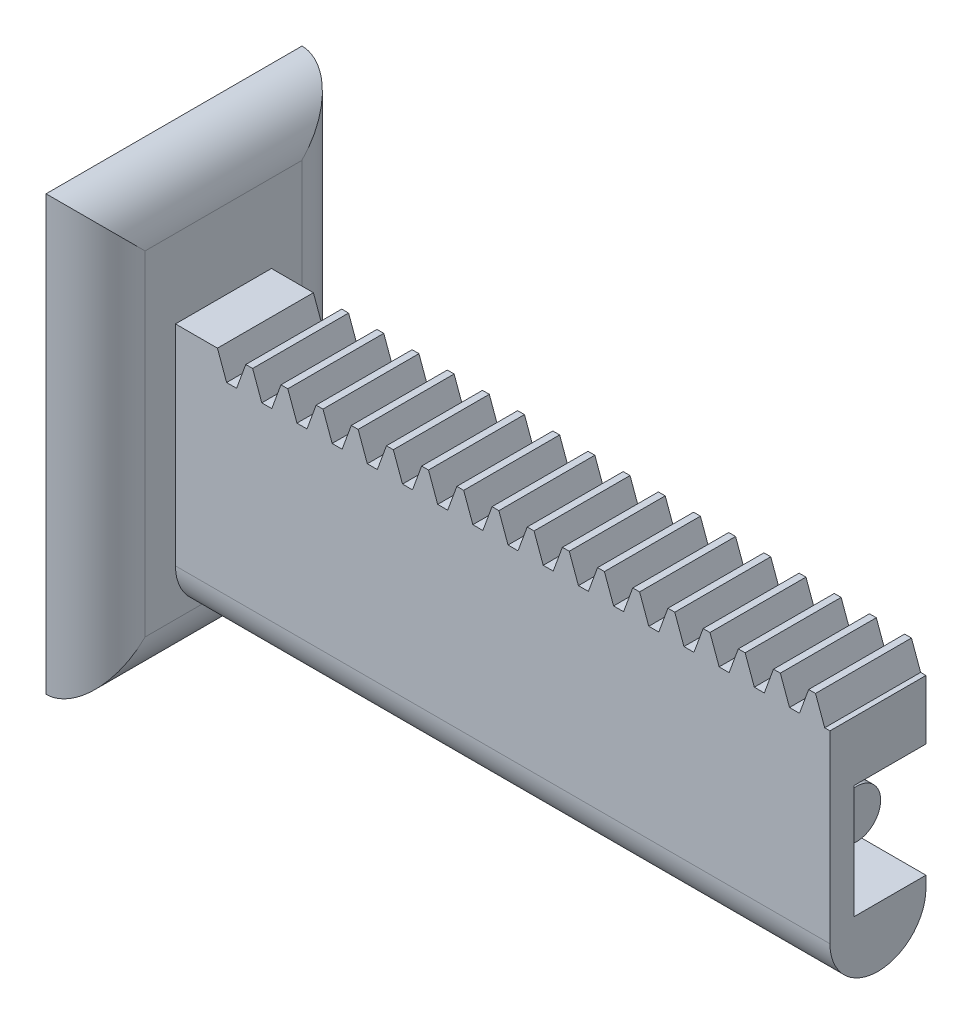
SolidWorks part; units mm, degrees
extrude "Blank" add sketch "BlankSke" against normal blind 4
sketch "BlankSke" plane through (0, 0, 0) normal (0, 0, 1) x (1, 0, 0)
  line L1 (0, 0) -> (44, 0)
  line L2 (0, 0) -> (0, 16.7)
  line L3 (0, 16.7) -> (44, 16.7)
  line L4 (44, 0) -> (44, 16.7)
  dimension "Length" = 44
  dimension "Blank_height" = 16.7
ref_plane "Plane1" through (0, 0, 0) normal (0, 0, 1) x (1, 0, 0)
ref_plane "Plane2" through (0, 0, 0) normal (0, 1, 0) x (1, 0, 0)
ref_plane "Plane3" through (0, 0, 0) normal (1, 0, 0) x (0, 0, -1)
sketch "HoldingSke" plane through (0, 0, 0) normal (0, 1, 0) x (1, 0, 0)
  line L0 (0, 0) -> (0.1988, 1.4147)
  line L1 (-15, 0) -> (100, 0) construction
  line L2 (0, 0) -> (-2.1039, 2.3779)
  line L3 (0, 0) -> (-11.863, 4.5341)
  line L4 (0, 0) -> (8.0072, 3.2351)
  line L5 (0, 0) -> (-23.7986, -8.8762)
  line L6 (0, 0) -> (-10.5278, -7.1032)
  line L9 (-71.009, 38.7566) -> (-29.6625, 53.8055)
  line L10 (-76.2, 3.0779) -> (-60.2, 3.0779)
  line L11 (0, 0) -> (-4, 0)
  line L12 (-76.2, 101.6) -> (-76.173, 101.6)
  line L13 (24.9733, 27.94) -> (52.9518, 28.4284)
  line L14 (24.9733, 27.94) -> (24.9743, 27.94)
  line L15 (24.9733, 27.94) -> (100.4006, 29.5858)
  circle A0 centre (0, 0) radius 19.05
  circle A1 centre (0, 0) radius 8
  circle A2 centre (0, 0) radius 12.7
  dimension "MPH" = 16
  dimension "Diameter" = 38.1
  dimension "Num_teeth" = 22
  dimension "Pitch" = 1.4286
  dimension "Show_teeth" = 998
  dimension "Thickness" = 12.7
  dimension "Ap" = 20
  dimension "Pitch_height" = 16
  dimension "Width" = 4
  dimension "Backlash" = 0.027
  dimension "Addendum_fac" = 1
  dimension "Dedendum_fac" = 1.25
  dimension "Clearance_fac" = 0.25
  dimension "Dedendum_add" = 0.001
  dimension "Length" = 44
  dimension "Module" = 0.7
sketch "TooCutSkeIll" plane through (0, 0, 0) normal (0, 0, 1) x (1, 0, 0)
  line L0 (-0.8789, 16.6816) -> (-0.3545, 15.2408)
  line L1 (-0.1891, 15.125) -> (0.1891, 15.125)
  line L2 (0.3545, 15.2408) -> (0.8789, 16.6816)
  line L3 (44, 16.7) -> (0, 16.7) construction
  line L4 (0, 0) -> (0, 64.897) construction
  line L5 (-13.208, 16) -> (12.954, 16) construction
  line L6 (0, 0) -> (44, 0) construction
  line L7 (0.6308, 16) -> (0.6308, 48.7463) construction
  line L8 (-0.6308, 16) -> (-0.6308, 48.7463) construction
  line L9 (0.9052, 16.7) -> (0.9052, 16.7254)
  line L10 (-0.9052, 16.7) -> (-0.9052, 16.7254)
  line L11 (-0.9052, 16.7254) -> (0.9052, 16.7254)
  arc A0 (0.1891, 15.125) -> (0.3545, 15.2408) centre (0.1891, 15.301) ccw
  arc A1 (-0.3545, 15.2408) -> (-0.1891, 15.125) centre (-0.1891, 15.301) ccw
  arc A2 (0.9052, 16.7) -> (0.8789, 16.6816) centre (0.9052, 16.672) ccw
  arc A3 (-0.8789, 16.6816) -> (-0.9052, 16.7) centre (-0.9052, 16.672) ccw
  dimension "Pitch_height" = 16
  dimension "Addendum_plus" = 0.7254
  dimension "Pressure_angle" = 20
  dimension "Gap_width" = 1.2616
  dimension "Dedendum" = 0.875
extrude "ToothCutIll" [suppressed] cut sketch "TooCutSkeIll" against normal through all
sketch "TooCutSkeSim" plane through (0, 0, 0) normal (0, 0, 1) x (1, 0, 0)
  line L0 (0.3123, 15.125) -> (-0.3123, 15.125)
  line L1 (0.8948, 16.7254) -> (0.3123, 15.125)
  line L2 (0, 17.4625) -> (0, 53.467) construction
  line L3 (0.8948, 16.7254) -> (-0.8948, 16.7254)
  line L6 (-0.8948, 16.7254) -> (-0.3123, 15.125)
  line L9 (-0.6308, 16) -> (0.6308, 16) construction
  line L10 (0, 0) -> (44, 0) construction
  line L11 (0.6308, 16) -> (0.6308, 53.467) construction
  line L12 (-0.6308, 16) -> (-0.6308, 53.467) construction
  dimension "Pitch_height" = 16
  dimension "Addendum_plus" = 0.7254
  dimension "Pressure_angle" = 20
  dimension "Gap_width" = 1.2616
  dimension "Dedendum" = 0.875
extrude "ToothCutSim" cut sketch "TooCutSkeSim" against normal through all
pattern_linear "TeethCuts" count 22 spacing 2.1991 along (1, 0, 0) of "ToothCutIll", "ToothCutSim"
sketch "Croquis1" plane through (0, 0, 0) normal (0, -1, 0) x (1, 0, 0)
  line L4 (44, 0) -> (0, 0)
  line L5 (0, 0) -> (0, -4)
  line L6 (0, -4) -> (44, -4)
  line L7 (44, -4) -> (44, 0)
  line L8 (44, 0) -> (0, 0)
  line L9 (0, 0) -> (0, -4)
  line L10 (0, -4) -> (44, -4)
  line L11 (44, -4) -> (44, 0)
  dimension "D1" = 0
sketch "Croquis2" plane through (0, 0, 0) normal (0, -1, 0) x (1, 0, 0)
  line L4 (44, 0) -> (0, 0)
  line L5 (0, 0) -> (0, -4)
  line L6 (0, -4) -> (44, -4)
  line L7 (44, -4) -> (44, 0)
  line L8 (44, 0) -> (0, 0)
  line L9 (0, 0) -> (0, -4)
  line L10 (0, -4) -> (44, -4)
  line L11 (44, -4) -> (44, 0)
  dimension "D1" = 0
extrude "Cortar-Extruir2" cut sketch "Croquis2" against normal blind 0.6
sketch "Croquis3" plane through (44, 0, 0) normal (1, 0, 0) x (0, 0, -1)
  line L0 (0, 7.8625) -> (4, 7.8625)
  line L1 (0, 0.6) -> (0, 15.125) construction
  line L2 (4, 0.6) -> (4, 15.125) construction
  line L3 (1.5, 4.3125) -> (1.5, 11.4125)
  line L5 (1.5, 11.4125) -> (4, 11.4125)
  line L6 (1.5, 11.4125) -> (1.5, 4.3125)
  line L7 (1.5, 4.3125) -> (4, 4.3125)
  line L8 (4, 11.4125) -> (4, 4.3125)
  point P9 (0, 7.8625)
  line M3 (0, 15.125) -> (0, 0.6)
  dimension "D1" = 2.5
  dimension "D2" = 7.1
extrude "Cortar-Extruir3" cut sketch "Croquis3" against normal blind 37 contours L8 L5 L0 M3 | L8 L0 L7 M3 region at (44, 9.6375, -2.75) region at (44, 6.0875, -2.75)
ref_plane "Plano1" through (0, 0, 0) normal (0, 0, 1) x (1, 0, 0)
sketch "Croquis4" plane through (0, 0, 0) normal (0, 0, 1) x (1, 0, 0)
  line L0 (0, 15.125) -> (0, 0.6) construction
  line L1 (5.7118, 15.125) -> (0, 15.125)
  line L2 (5.7118, 15.125) -> (5.7118, 16.7)
  line L3 (5.7118, 16.7) -> (0, 16.7)
  line L4 (0, 15.125) -> (0, 16.7)
extrude "Saliente-Extruir4" add sketch "Croquis4" against normal up to vertex (4 mm away) up to point (5.7118, 16.7, -4)
sketch "Croquis5" plane through (0, 0, -1.5) normal (0, 0, -1) x (-1, 0, 0)
  line L0 (-44, 7.8625) -> (-39.57, 7.8625) construction
  line L1 (-44, 4.3125) -> (-44, 11.4125) construction
  line L2 (-39.57, 5.7125) -> (-39.57, 10.0125) construction
  line L4 (-39.57, 10.0125) -> (-38.45, 10.0125)
  line L5 (-39.57, 5.7125) -> (-38.45, 5.7125)
  line L6 (-38.45, 10.0125) -> (-38.45, 5.7125)
  line L7 (-39.57, 10.0125) -> (-39.57, 5.7125)
  point P7 (-39.57, 7.8625)
  point P9 (-39.57, 7.8625)
  dimension "D1" = 4.43
  dimension "D2" = 4.3
  dimension "D3" = 1.12
  dimension "D4" = 1.12
extrude "Saliente-Extruir5" add sketch "Croquis5" along normal blind 4.2
sketch "Croquis14" plane through (39.57, 0, 0) normal (1, 0, 0) x (0, 0, -1)
  line L0 (5.7, 7.8625) -> (1.5, 7.8625) construction
  line L1 (5.7, 10.0125) -> (5.7, 5.7125) construction
  line L2 (1.5, 10.0125) -> (1.5, 5.7125) construction
  circle A0 centre (3.6, 7.8625) radius 1.5
  dimension "D1" = 3
extrude "Saliente-Extruir11" add sketch "Croquis14" along normal blind 2.5
sketch "Croquis13" plane through (39.57, 0, 0) normal (1, 0, 0) x (0, 0, -1)
  line L0 (5.7, 7.8625) -> (1.5, 7.8625) construction
  line L1 (5.7, 10.0125) -> (5.7, 5.7125) construction
  line L2 (1.5, 10.0125) -> (1.5, 5.7125) construction
  circle A0 centre (3.6, 7.8625) radius 0.75
  dimension "D1" = 1.5
sketch "Croquis15" plane through (0, 0, 0) normal (0, 0, 1) x (1, 0, 0)
  line L0 (44, 0.6) -> (0, 0.6) construction
  line L1 (0, 16.7) -> (3.0889, 16.7)
  line L2 (0, 16.7) -> (0, 0.6)
  line L3 (0, 0.6) -> (3.0889, 0.6)
  line L4 (3.0889, 16.7) -> (3.0889, 0.6)
extrude "Saliente-Extruir12" add sketch "Croquis15" along normal blind 5
sketch "Croquis16" plane through (0, 0, -4) normal (0, 0, -1) x (-1, 0, 0)
  line L0 (-5.7118, 16.7) -> (0, 16.7) construction
  line L1 (0, 0.6) -> (-2.8559, 0.6)
  line L2 (0, 0.6) -> (0, 16.7)
  line L3 (0, 16.7) -> (-2.8559, 16.7)
  line L4 (-2.8559, 0.6) -> (-2.8559, 16.7)
extrude "Saliente-Extruir13" add sketch "Croquis16" along normal blind 5
sketch "Croquis17" plane through (0, 0, -4) normal (0, 0, -1) x (-1, 0, 0)
  line L78 (-44, 0.6) -> (-2.8559, 0.6)
  line L79 (-2.8559, 0.6) -> (-2.8559, 16.7)
  line L80 (-2.8559, 16.7) -> (-5.7118, 16.7)
  line L81 (-5.7118, 16.7) -> (-6.285, 15.125)
  line L82 (-6.285, 15.125) -> (-6.9096, 15.125)
  line L83 (-6.9096, 15.125) -> (-7.4829, 16.7)
  line L84 (-7.4829, 16.7) -> (-7.9109, 16.7)
  line L85 (-7.9109, 16.7) -> (-8.4842, 15.125)
  line L86 (-8.4842, 15.125) -> (-9.1088, 15.125)
  line L87 (-9.1088, 15.125) -> (-9.682, 16.7)
  line L88 (-9.682, 16.7) -> (-10.11, 16.7)
  line L89 (-10.11, 16.7) -> (-10.6833, 15.125)
  line L90 (-10.6833, 15.125) -> (-11.3079, 15.125)
  line L91 (-11.3079, 15.125) -> (-11.8811, 16.7)
  line L92 (-11.8811, 16.7) -> (-12.3091, 16.7)
  line L93 (-12.3091, 16.7) -> (-12.8824, 15.125)
  line L94 (-12.8824, 15.125) -> (-13.507, 15.125)
  line L95 (-13.507, 15.125) -> (-14.0802, 16.7)
  line L96 (-14.0802, 16.7) -> (-14.5082, 16.7)
  line L97 (-14.5082, 16.7) -> (-15.0815, 15.125)
  line L98 (-15.0815, 15.125) -> (-15.7061, 15.125)
  line L99 (-15.7061, 15.125) -> (-16.2794, 16.7)
  line L100 (-16.2794, 16.7) -> (-16.7074, 16.7)
  line L101 (-16.7074, 16.7) -> (-17.2806, 15.125)
  line L102 (-17.2806, 15.125) -> (-17.9052, 15.125)
  line L103 (-17.9052, 15.125) -> (-18.4785, 16.7)
  line L104 (-18.4785, 16.7) -> (-18.9065, 16.7)
  line L105 (-18.9065, 16.7) -> (-19.4797, 15.125)
  line L106 (-19.4797, 15.125) -> (-20.1043, 15.125)
  line L107 (-20.1043, 15.125) -> (-20.6776, 16.7)
  line L108 (-20.6776, 16.7) -> (-21.1056, 16.7)
  line L109 (-21.1056, 16.7) -> (-21.6788, 15.125)
  line L110 (-21.6788, 15.125) -> (-22.3035, 15.125)
  line L111 (-22.3035, 15.125) -> (-22.8767, 16.7)
  line L112 (-22.8767, 16.7) -> (-23.3047, 16.7)
  line L113 (-23.3047, 16.7) -> (-23.878, 15.125)
  line L114 (-23.878, 15.125) -> (-24.5026, 15.125)
  line L115 (-24.5026, 15.125) -> (-25.0758, 16.7)
  line L116 (-25.0758, 16.7) -> (-25.5038, 16.7)
  line L117 (-25.5038, 16.7) -> (-26.0771, 15.125)
  line L118 (-26.0771, 15.125) -> (-26.7017, 15.125)
  line L119 (-26.7017, 15.125) -> (-27.2749, 16.7)
  line L120 (-27.2749, 16.7) -> (-27.7029, 16.7)
  line L121 (-27.7029, 16.7) -> (-28.2762, 15.125)
  line L122 (-28.2762, 15.125) -> (-28.9008, 15.125)
  line L123 (-28.9008, 15.125) -> (-29.4741, 16.7)
  line L124 (-29.4741, 16.7) -> (-29.9021, 16.7)
  line L125 (-29.9021, 16.7) -> (-30.4753, 15.125)
  line L126 (-30.4753, 15.125) -> (-31.0999, 15.125)
  line L127 (-31.0999, 15.125) -> (-31.6732, 16.7)
  line L128 (-31.6732, 16.7) -> (-32.1012, 16.7)
  line L129 (-32.1012, 16.7) -> (-32.6744, 15.125)
  line L130 (-32.6744, 15.125) -> (-33.299, 15.125)
  line L131 (-33.299, 15.125) -> (-33.8723, 16.7)
  line L132 (-33.8723, 16.7) -> (-34.3003, 16.7)
  line L133 (-34.3003, 16.7) -> (-34.8735, 15.125)
  line L134 (-34.8735, 15.125) -> (-35.4981, 15.125)
  line L135 (-35.4981, 15.125) -> (-36.0714, 16.7)
  line L136 (-36.0714, 16.7) -> (-36.4994, 16.7)
  line L137 (-36.4994, 16.7) -> (-37.0726, 15.125)
  line L138 (-37.0726, 15.125) -> (-37.6973, 15.125)
  line L139 (-37.6973, 15.125) -> (-38.2705, 16.7)
  line L140 (-38.2705, 16.7) -> (-38.6985, 16.7)
  line L141 (-38.6985, 16.7) -> (-39.2718, 15.125)
  line L142 (-39.2718, 15.125) -> (-39.8964, 15.125)
  line L143 (-39.8964, 15.125) -> (-40.4696, 16.7)
  line L144 (-40.4696, 16.7) -> (-40.8976, 16.7)
  line L145 (-40.8976, 16.7) -> (-41.4709, 15.125)
  line L146 (-41.4709, 15.125) -> (-42.0955, 15.125)
  line L147 (-42.0955, 15.125) -> (-42.6687, 16.7)
  line L148 (-42.6687, 16.7) -> (-43.0967, 16.7)
  line L149 (-43.0967, 16.7) -> (-43.67, 15.125)
  line L150 (-43.67, 15.125) -> (-44, 15.125)
  line L151 (-44, 15.125) -> (-44, 11.4125)
  line L152 (-44, 11.4125) -> (-7, 11.4125)
  line L153 (-7, 11.4125) -> (-7, 4.3125)
  line L154 (-7, 4.3125) -> (-44, 4.3125)
  line L155 (-44, 4.3125) -> (-44, 0.6)
  line L156 (-44, 0.6) -> (-2.8559, 0.6)
  line L157 (-2.8559, 0.6) -> (-2.8559, 16.7)
  line L158 (-2.8559, 16.7) -> (-5.7118, 16.7)
  line L159 (-5.7118, 16.7) -> (-6.285, 15.125)
  line L160 (-6.285, 15.125) -> (-6.9096, 15.125)
  line L161 (-6.9096, 15.125) -> (-7.4829, 16.7)
  line L162 (-7.4829, 16.7) -> (-7.9109, 16.7)
  line L163 (-7.9109, 16.7) -> (-8.4842, 15.125)
  line L164 (-8.4842, 15.125) -> (-9.1088, 15.125)
  line L165 (-9.1088, 15.125) -> (-9.682, 16.7)
  line L166 (-9.682, 16.7) -> (-10.11, 16.7)
  line L167 (-10.11, 16.7) -> (-10.6833, 15.125)
  line L168 (-10.6833, 15.125) -> (-11.3079, 15.125)
  line L169 (-11.3079, 15.125) -> (-11.8811, 16.7)
  line L170 (-11.8811, 16.7) -> (-12.3091, 16.7)
  line L171 (-12.3091, 16.7) -> (-12.8824, 15.125)
  line L172 (-12.8824, 15.125) -> (-13.507, 15.125)
  line L173 (-13.507, 15.125) -> (-14.0802, 16.7)
  line L174 (-14.0802, 16.7) -> (-14.5082, 16.7)
  line L175 (-14.5082, 16.7) -> (-15.0815, 15.125)
  line L176 (-15.0815, 15.125) -> (-15.7061, 15.125)
  line L177 (-15.7061, 15.125) -> (-16.2794, 16.7)
  line L178 (-16.2794, 16.7) -> (-16.7074, 16.7)
  line L179 (-16.7074, 16.7) -> (-17.2806, 15.125)
  line L180 (-17.2806, 15.125) -> (-17.9052, 15.125)
  line L181 (-17.9052, 15.125) -> (-18.4785, 16.7)
  line L182 (-18.4785, 16.7) -> (-18.9065, 16.7)
  line L183 (-18.9065, 16.7) -> (-19.4797, 15.125)
  line L184 (-19.4797, 15.125) -> (-20.1043, 15.125)
  line L185 (-20.1043, 15.125) -> (-20.6776, 16.7)
  line L186 (-20.6776, 16.7) -> (-21.1056, 16.7)
  line L187 (-21.1056, 16.7) -> (-21.6788, 15.125)
  line L188 (-21.6788, 15.125) -> (-22.3035, 15.125)
  line L189 (-22.3035, 15.125) -> (-22.8767, 16.7)
  line L190 (-22.8767, 16.7) -> (-23.3047, 16.7)
  line L191 (-23.3047, 16.7) -> (-23.878, 15.125)
  line L192 (-23.878, 15.125) -> (-24.5026, 15.125)
  line L193 (-24.5026, 15.125) -> (-25.0758, 16.7)
  line L194 (-25.0758, 16.7) -> (-25.5038, 16.7)
  line L195 (-25.5038, 16.7) -> (-26.0771, 15.125)
  line L196 (-26.0771, 15.125) -> (-26.7017, 15.125)
  line L197 (-26.7017, 15.125) -> (-27.2749, 16.7)
  line L198 (-27.2749, 16.7) -> (-27.7029, 16.7)
  line L199 (-27.7029, 16.7) -> (-28.2762, 15.125)
  line L200 (-28.2762, 15.125) -> (-28.9008, 15.125)
  line L201 (-28.9008, 15.125) -> (-29.4741, 16.7)
  line L202 (-29.4741, 16.7) -> (-29.9021, 16.7)
  line L203 (-29.9021, 16.7) -> (-30.4753, 15.125)
  line L204 (-30.4753, 15.125) -> (-31.0999, 15.125)
  line L205 (-31.0999, 15.125) -> (-31.6732, 16.7)
  line L206 (-31.6732, 16.7) -> (-32.1012, 16.7)
  line L207 (-32.1012, 16.7) -> (-32.6744, 15.125)
  line L208 (-32.6744, 15.125) -> (-33.299, 15.125)
  line L209 (-33.299, 15.125) -> (-33.8723, 16.7)
  line L210 (-33.8723, 16.7) -> (-34.3003, 16.7)
  line L211 (-34.3003, 16.7) -> (-34.8735, 15.125)
  line L212 (-34.8735, 15.125) -> (-35.4981, 15.125)
  line L213 (-35.4981, 15.125) -> (-36.0714, 16.7)
  line L214 (-36.0714, 16.7) -> (-36.4994, 16.7)
  line L215 (-36.4994, 16.7) -> (-37.0726, 15.125)
  line L216 (-37.0726, 15.125) -> (-37.6973, 15.125)
  line L217 (-37.6973, 15.125) -> (-38.2705, 16.7)
  line L218 (-38.2705, 16.7) -> (-38.6985, 16.7)
  line L219 (-38.6985, 16.7) -> (-39.2718, 15.125)
  line L220 (-39.2718, 15.125) -> (-39.8964, 15.125)
  line L221 (-39.8964, 15.125) -> (-40.4696, 16.7)
  line L222 (-40.4696, 16.7) -> (-40.8976, 16.7)
  line L223 (-40.8976, 16.7) -> (-41.4709, 15.125)
  line L224 (-41.4709, 15.125) -> (-42.0955, 15.125)
  line L225 (-42.0955, 15.125) -> (-42.6687, 16.7)
  line L226 (-42.6687, 16.7) -> (-43.0967, 16.7)
  line L227 (-43.0967, 16.7) -> (-43.67, 15.125)
  line L228 (-43.67, 15.125) -> (-44, 15.125)
  line L229 (-44, 15.125) -> (-44, 11.4125)
  line L230 (-44, 11.4125) -> (-7, 11.4125)
  line L231 (-7, 11.4125) -> (-7, 4.3125)
  line L232 (-7, 4.3125) -> (-44, 4.3125)
  line L233 (-44, 4.3125) -> (-44, 0.6)
  dimension "D1" = 0
extrude "Saliente-Extruir14" add sketch "Croquis17" along normal blind 2
sketch "Croquis18" plane through (38.45, 0, 0) normal (-1, 0, 0) x (0, 0, 1)
  line L4 (-1.5, 5.7125) -> (-1.5, 10.0125)
  line L5 (-1.5, 10.0125) -> (-5.7, 10.0125)
  line L6 (-5.7, 10.0125) -> (-5.7, 5.7125)
  line L7 (-5.7, 5.7125) -> (-1.5, 5.7125)
  line L8 (-1.5, 5.7125) -> (-1.5, 10.0125)
  line L9 (-1.5, 10.0125) -> (-5.7, 10.0125)
  line L10 (-5.7, 10.0125) -> (-5.7, 5.7125)
  line L11 (-5.7, 5.7125) -> (-1.5, 5.7125)
  dimension "D1" = 0
extrude "Saliente-Extruir15" add sketch "Croquis18" along normal blind 2
sketch "Croquis19" plane through (0, 16.7, 0) normal (0, 1, 0) x (1, 0, 0)
  line L0 (2.8559, 9) -> (2.8559, 6) construction
  line L1 (0, 9) -> (2.8559, 9)
  line L2 (0, 9) -> (0, -5)
  line L3 (0, -5) -> (2.8559, -5)
  line L4 (2.8559, 9) -> (2.8559, -5)
  line L5 (0, 9) -> (2.8559, 9) construction
extrude "Saliente-Extruir16" add sketch "Croquis19" along normal blind 8
sketch "Croquis20" plane through (0, 0, -9) normal (0, 0, -1) x (-1, 0, 0)
  line L4 (0, 0.6) -> (0, 24.7)
  line L5 (0, 24.7) -> (-2.8559, 24.7)
  line L6 (-2.8559, 24.7) -> (-2.8559, 0.6)
  line L7 (-2.8559, 0.6) -> (0, 0.6)
  line L8 (0, 0.6) -> (0, 24.7)
  line L9 (0, 24.7) -> (-2.8559, 24.7)
  line L10 (-2.8559, 24.7) -> (-2.8559, 0.6)
  line L11 (-2.8559, 0.6) -> (0, 0.6)
  dimension "D1" = 0
extrude "Saliente-Extruir18" add sketch "Croquis20" along normal blind 2
sketch "Croquis21" plane through (0, 0.6, 0) normal (0, -1, 0) x (1, 0, 0)
  line L0 (3.0889, 0) -> (2.8559, -6)
  line L1 (0, 5) -> (0, -11) construction
  line L2 (2.8559, -11) -> (2.8559, -6) construction
  line L3 (2.8559, -11) -> (0, -11) construction
  line L4 (0, 5) -> (3.0889, 5) construction
  line L5 (3.0889, 5) -> (3.0889, 0) construction
  line L6 (0, 5) -> (0, -11)
  line L7 (2.8559, -11) -> (2.8559, -6)
  line L8 (2.8559, -11) -> (0, -11)
  line L9 (0, 5) -> (3.0889, 5)
  line L10 (3.0889, 5) -> (3.0889, 0)
extrude "Saliente-Extruir19" add sketch "Croquis21" along normal blind 3
ref_plane "Plano2" through (0, 0, 0) normal (-1, 0, 0) x (0, 0, 1)
sketch "Croquis22" plane through (0, 0, 0) normal (-1, 0, 0) x (0, 0, 1)
  line L4 (5, -2.4) -> (5, 24.7)
  line L5 (5, 24.7) -> (-11, 24.7)
  line L6 (-11, 24.7) -> (-11, -2.4)
  line L7 (-11, -2.4) -> (5, -2.4)
  line L8 (5, -2.4) -> (5, 24.7)
  line L9 (5, 24.7) -> (-11, 24.7)
  line L10 (-11, 24.7) -> (-11, -2.4)
  line L11 (-11, -2.4) -> (5, -2.4)
  dimension "D1" = 0
sketch "Croquis26" plane through (0, 0, 0) normal (-1, 0, 0) x (0, 0, 1)
  line L4 (5, -2.4) -> (5, 24.7)
  line L5 (5, 24.7) -> (-11, 24.7)
  line L6 (-11, 24.7) -> (-11, -2.4)
  line L7 (-11, -2.4) -> (5, -2.4)
  line L8 (5, -2.4) -> (5, 24.7)
  line L9 (5, 24.7) -> (-11, 24.7)
  line L10 (-11, 24.7) -> (-11, -2.4)
  line L11 (-11, -2.4) -> (5, -2.4)
  dimension "D1" = 0
ref_plane "Plano3" through (2.8559, 0.6, -6) normal (0.0388, 0, 0.9992) x (0.9992, 0, -0.0388)
ref_plane "Plano4" through (0, 0, 0) normal (-1, 0, 0) x (0, 0, 1)
sketch "Croquis29" plane through (0, 0, 0) normal (-1, 0, 0) x (0, 0, 1)
  line L4 (5, -2.4) -> (5, 24.7)
  line L5 (5, 24.7) -> (-11, 24.7)
  line L6 (-11, 24.7) -> (-11, -2.4)
  line L7 (-11, -2.4) -> (5, -2.4)
  line L8 (5, -2.4) -> (5, 24.7)
  line L9 (5, 24.7) -> (-11, 24.7)
  line L10 (-11, 24.7) -> (-11, -2.4)
  line L11 (-11, -2.4) -> (5, -2.4)
  dimension "D1" = 0
sketch "Croquis31" plane through (0, 0, -11) normal (0, 0, -1) x (-1, 0, 0)
  line L4 (-2.8559, 24.7) -> (-2.8559, -2.4)
  line L5 (-2.8559, -2.4) -> (0, -2.4)
  line L6 (0, -2.4) -> (0, 24.7)
  line L7 (0, 24.7) -> (-2.8559, 24.7)
  line L8 (-2.8559, 24.7) -> (-2.8559, -2.4)
  line L9 (-2.8559, -2.4) -> (0, -2.4)
  line L10 (0, -2.4) -> (0, 24.7)
  line L11 (0, 24.7) -> (-2.8559, 24.7)
  dimension "D1" = 0
extrude "Saliente-Extruir20" add sketch "Croquis31" against normal up to vertex (16 mm away) up to point (3.0889, -2.4, 5)
sketch "Croquis32" plane through (0, 0, 5) normal (0, 0, 1) x (1, 0, 0)
  line L1 (3.0889, -2.4) -> (0, -2.4)
  line L2 (3.0889, -2.4) -> (3.0889, 24.7)
  line L3 (3.0889, 24.7) -> (0, 24.7)
  line L4 (0, -2.4) -> (0, 24.7)
extrude "Saliente-Extruir21" add sketch "Croquis32" against normal up to vertex (16 mm away) up to point (2.8559, 24.7, -11)
fillet "Redondeo3" radius 3 2 edges at (23.5445, 0.6, -6) (23.5445, 0.6, 0)
fillet "Redondeo4" radius 3.1 4 edges at (3.0889, -2.4, -3) (3.0889, 11.15, 5) (3.0889, 24.7, -3) (3.0889, 11.15, -11)
ref_plane "Plano5" through (7, 0, 0) normal (1, 0, 0) x (0, 0, -1)
sketch "Croquis33" plane through (7, 0, 0) normal (1, 0, 0) x (0, 0, -1)
  line L1 (5.861, 3.6) -> (6, 3.6)
  line L2 (0, 3.6) -> (0, 16.7)
  line L3 (0, 16.7) -> (6, 16.7)
  line L4 (6, 3.6) -> (6, 16.7)
  arc A0 (0, 3.6) -> (5.861, 3.6) centre (2.9305, 3.6) ccw
equation "' \"Module@HoldingSke\" = 6.35"
equation "' \"Num_teeth@HoldingSke\" = 12"
equation "' \"Ap@HoldingSke\" =  20"
equation "' \"Ap@HoldingSke\" = 20"
equation "' \"Width@HoldingSke\" = 0.25 * 25.4"
equation "' \"Show_teeth@HoldingSke\" = 500"
equation "' \"Backlash@HoldingSke\" = 0.009 * 25.4"
equation "' \"Addendum_fac@HoldingSke\" = 1.0"
equation "' \"Dedendum_fac@HoldingSke\" = 1.25"
equation "' \"Dedendum_add@HoldingSke\" = 0.00005 * 25.4"
equation "' \"Clearance_fac@HoldingSke\" = 0.25"
equation "' \"Pitch_height@HoldingSke\" = 1 * 25.4"
equation "' \"Length@HoldingSke\" = 4.71 * 25.4"
equation "\"Pitch@HoldingSke\" = 1 / \"Module@HoldingSke\""
equation "\"MPH@HoldingSke\" = \"Dedendum_fac@HoldingSke\" / \"Pitch@HoldingSke\" + 2 * \"Dedendum_add@HoldingSke\" + 0.002 * 25.4"
equation "\"MPH@HoldingSke\" = ((sgn( \"MPH@HoldingSke\" - \"Pitch_height@HoldingSke\")+1)*( \"MPH@HoldingSke\" - \"Pitch_height@HoldingSke\"))/2 + \"Pitch_height@HoldingSke\""
equation "\"Blank_height@BlankSke\" = \"Pitch_height@HoldingSke\" + \"Addendum_fac@HoldingSke\"  / \"Pitch@HoldingSke\" "
equation "\"Length@BlankSke\" =  \"Length@HoldingSke\""
equation "\"Face_width@Blank\" = \"Width@HoldingSke\""
equation "\"Pressure_angle@TooCutSkeIll\" = \"Ap@HoldingSke\""
equation "\"Addendum_plus@TooCutSkeIll\" =  \"Addendum_fac@HoldingSke\"  / \"Pitch@HoldingSke\" + 0.001 *25.4"
equation "\"Dedendum@TooCutSkeIll\" = \"Dedendum_fac@HoldingSke\"  / \"Pitch@HoldingSke\""
equation "\"Pitch_height@TooCutSkeIll\" =  \"MPH@HoldingSke\""
equation "\"Gap_width@TooCutSkeIll\" = 3.14159265 / 2 / \"Pitch@HoldingSke\" + 6 * \"Backlash@HoldingSke\""
equation "\"Pressure_angle@TooCutSkeSim\" = \"Ap@HoldingSke\""
equation "\"Addendum_plus@TooCutSkeSim\" =  \"Addendum_fac@HoldingSke\"  / \"Pitch@HoldingSke\" + 0.001 * 25.4"
equation "\"Dedendum@TooCutSkeSim\" = \"Dedendum_fac@HoldingSke\"  / \"Pitch@HoldingSke\""
equation "\"Pitch_height@TooCutSkeSim\" =  \"MPH@HoldingSke\""
equation "\"Gap_width@TooCutSkeSim\" = 3.14159265 / 2 / \"Pitch@HoldingSke\" + 6 * \"Backlash@HoldingSke\""
equation "\"Root_fillet@TooCutSkeIll\" = \"Clearance_fac@HoldingSke\" / \"Pitch@HoldingSke\" + \"Dedendum_add@HoldingSke\""
equation "\"Break_rad@TooCutSkeIll\" = 0.02 / \"Pitch@HoldingSke\" * 2"
equation "\"Linear_pitch@TeethCuts\" = 3.14159265 / \"Pitch@HoldingSke\""
equation "\"Num_teeth@HoldingSke\" = int( ( \"Length@HoldingSke\" + 0 ) / (3.14159265 / \"Pitch@HoldingSke\")) + 0.9999  + 1"
equation " \"Num_teeth@TeethCuts\" = int( \"Show_teeth@HoldingSke\" ) + 1"
equation " \"Num_teeth@TeethCuts\" = ((sgn( \"Num_teeth@TeethCuts\" - \"Num_teeth@HoldingSke\" )-1)*( \"Num_teeth@TeethCuts\" - \"Num_teeth@HoldingSke\" ))/-2+ \"Num_teeth@HoldingSke\""
equation " \"Num_teeth@TeethCuts\" = ((sgn( \"Num_teeth@TeethCuts\" - 2.0)+1)*( \"Num_teeth@TeethCuts\" - 2.0))/2 +2.0"
